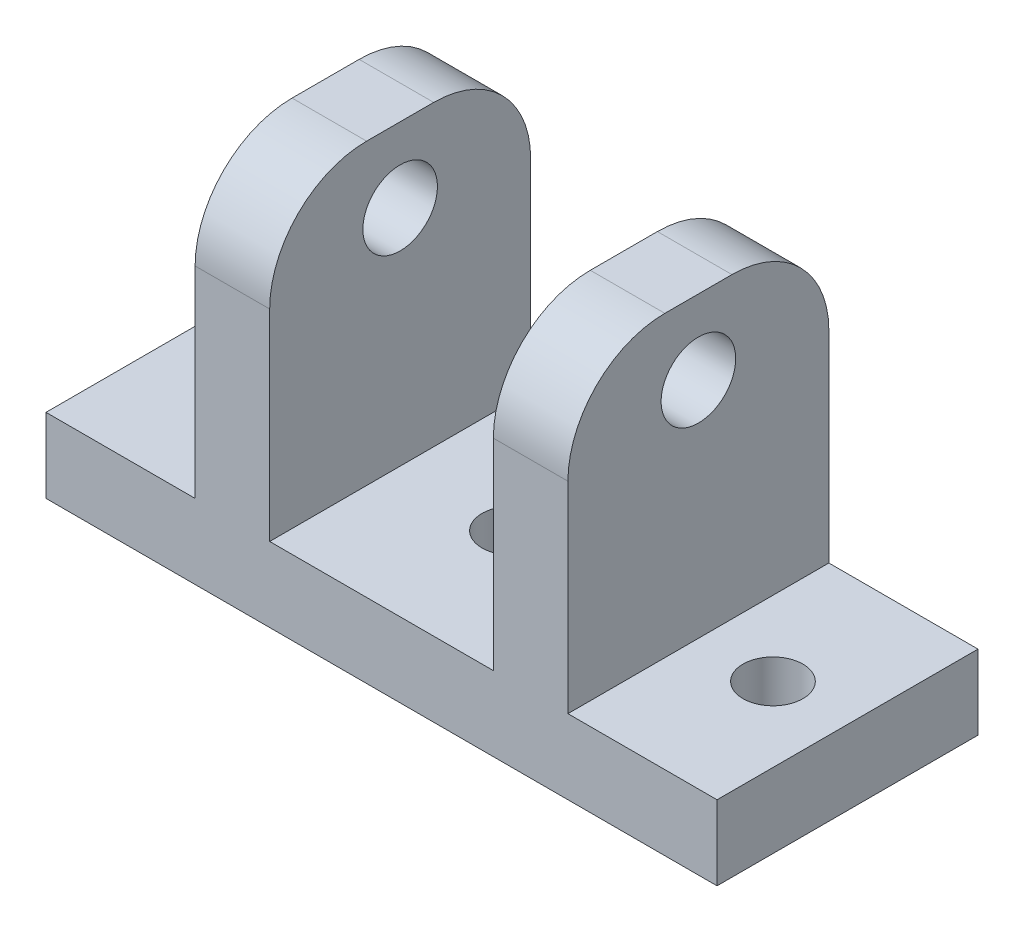
SolidWorks part; units mm, degrees
ref_plane "Front Plane" through (0, 0, 0) normal (0, 0, 1) x (1, 0, 0)
ref_plane "Top Plane" through (0, 0, 0) normal (0, 1, 0) x (1, 0, 0)
ref_plane "Right Plane" through (0, 0, 0) normal (1, 0, 0) x (0, 0, -1)
sketch "Sketch2" plane through (0, 0, 0) normal (0, 1, 0) x (1, 0, 0)
  line L0 (12.7, 22.225) -> (12.7, 0)
  line L1 (0, 0) -> (57.15, 0)
  line L2 (0, 0) -> (0, 22.225)
  line L3 (0, 22.225) -> (57.15, 22.225)
  line L4 (57.15, 0) -> (57.15, 22.225)
  line L5 (19.05, 22.225) -> (19.05, 0)
  line L6 (38.1, 22.225) -> (38.1, 0)
  line L7 (44.45, 22.225) -> (44.45, 0)
  dimension "D1" = 57.15
  dimension "D2" = 22.225
  dimension "D3" = 12.7
  dimension "D4" = 6.35
  dimension "D5" = 12.7
  dimension "D6" = 6.35
extrude "Boss-Extrude1" add sketch "Sketch2" along normal blind 6.35 contours L3 L2 L1 L0 | L3 L7 L1 L4 | L6 L3 L5 L1 region at (6.35, 0, -11.1125) region at (28.575, 0, -11.1125) region at (50.8, 0, -11.1125)
extrude "Boss-Extrude2" add sketch "Sketch2<3>" along normal blind 31.75 contours L5 L3 L0 L1 | L7 L3 L6 L1 region at (15.875, 0, -11.1125) region at (41.275, 0, -11.1125)
sketch "Sketch2<3>" plane through (0, 0, 0) normal (0, 1, 0) x (1, 0, 0) same geometry as "Sketch2"
sketch "Sketch3" plane through (12.7, 0, 0) normal (-1, 0, 0) x (0, 0, 1)
  line L0 (-22.225, 6.35) -> (-6.35, 6.35)
  line L1 (-22.225, 6.35) -> (0, 6.35) construction
  line L3 (-22.225, 31.75) -> (0, 31.75) construction
  line L4 (-22.225, 6.35) -> (0, 6.35)
  line L5 (-22.225, 6.35) -> (-22.225, 31.75)
  line L6 (-22.225, 31.75) -> (0, 31.75)
  line L7 (0, 6.35) -> (0, 31.75)
  line L8 (-11.1125, 31.75) -> (-11.1125, 25.4) construction
  circle A0 centre (-11.1125, 25.4) radius 3.175
  dimension "D5" = 6.35
  dimension "D2" = 6.35
  dimension "D3" = 22.225
  dimension "D4" = 6.35
extrude "Cut-Extrude1" cut sketch "Sketch3" against normal through all contours A0 region at (12.7, 25.4, -11.1125)
sketch "Sketch4" plane through (0, 6.35, 0) normal (0, 1, 0) x (1, 0, 0)
  line L0 (0, 11.1125) -> (57.15, 11.1125) construction
  line L1 (0, 0) -> (0, 22.225) construction
  line L2 (57.15, 0) -> (57.15, 22.225) construction
  circle A0 centre (6.35, 11.1125) radius 6.35
  circle A1 centre (28.575, 11.1125) radius 6.35
  circle A2 centre (50.8, 11.1125) radius 6.35
  dimension "D1" = 12.7
  dimension "D2" = 12.7
  dimension "D3" = 12.7
hole_wizard "1/4-20 Tapped Hole1" positions "3DSketch1" profile "Sketch5" tap size "1/4-20" standard "ANSI Inch"
sketch3d "3DSketch1"
  point P0 (6.35, 6.35, -11.1125)
  point P3 (28.575, 6.35, -11.1125)
  point P6 (50.8, 6.35, -11.1125)
sketch "Sketch5" plane through (6.35, 6.35, -11.1125) normal (1, 0, 0) x (0, 0, 1)
  line L0 (0, 0) -> (0, 20.5838)
  line L1 (0, 20.5838) -> (2.5527, 19.05)
  line L2 (2.5527, 19.05) -> (2.5527, 0)
  line L5 (2.5527, 0) -> (0, 0)
  line L10 (0, 20.5838) -> (-2.5527, 19.05) construction
  line L11 (0, -6.35) -> (0, 107.95) construction
  dimension "Tap Drill Dia." = 5.1054
  dimension "Tap Drill Depth" = 19.05
  dimension "Drill Angle" = 118
cosmetic thread "Hole Thread1" parameters "D1"=6.35, "D2"=6.35
cosmetic thread "Hole Thread2" parameters "D1"=6.35, "D2"=6.35
cosmetic thread "Hole Thread3" parameters "D1"=6.35, "D2"=6.35
fillet "Fillet1" radius 8.255 4 edges at (15.875, 31.75, -22.225) (41.275, 31.75, -22.225) (41.275, 31.75, 0) (15.875, 31.75, 0)
